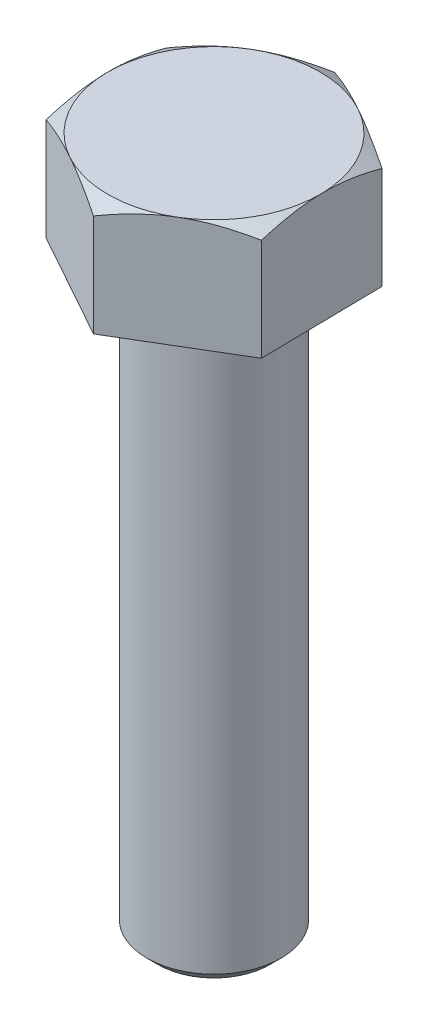
SolidWorks part; units mm, degrees
ref_plane "Front Plane" through (0, 0, 0) normal (0, 0, 1) x (1, 0, 0)
ref_plane "Top Plane" through (0, 0, 0) normal (0, 1, 0) x (1, 0, 0)
ref_plane "Right Plane" through (0, 0, 0) normal (1, 0, 0) x (0, 0, -1)
sketch "Sketch2" plane through (0, 0, 0) normal (0, 1, 0) x (1, 0, 0)
  line L0 (0, 72.9942) -> (0, -83.7037) construction
  line L1 (-114.1415, 0) -> (135.2788, 0) construction
  circle A0 centre (0, 0) radius 6
extrude "Boss-Extrude1" add sketch "Sketch2" against normal blind 52
sketch "Sketch3" plane through (0, 0, 0) normal (0, 1, 0) x (1, 0, 0)
  line L1 (9.5854, -5.3341) -> (9.4122, 5.6342)
  line L2 (9.4122, 5.6342) -> (-0.1733, 10.9683)
  line L3 (-0.1733, 10.9683) -> (-9.5854, 5.3341)
  line L4 (-9.5854, 5.3341) -> (-9.4122, -5.6342)
  line L5 (-9.4122, -5.6342) -> (0.1733, -10.9683)
  line L6 (0.1733, -10.9683) -> (9.5854, -5.3341)
  circle A0 centre (0, 0) radius 9.5 construction
  dimension "D1" = 19
extrude "Boss-Extrude2" add sketch "Sketch3" along normal blind 10
ref_axis "Axis1" through (0, -52, 0) along (0, 1, 0)
sketch "Sketch5" plane through (0, 10, 0) normal (0, 1, 0) x (1, 0, 0)
  line L0 (9.4122, 5.6342) -> (-0.1733, 10.9683) construction
  circle A0 centre (0, 0) radius 9.5
extrude "Cut-Extrude1" cut sketch "Sketch5" against normal blind 10 draft 60 flip side to cut
chamfer "Chamfer1" distance 1 angle 45 1 edges at (0, -52, 6)
